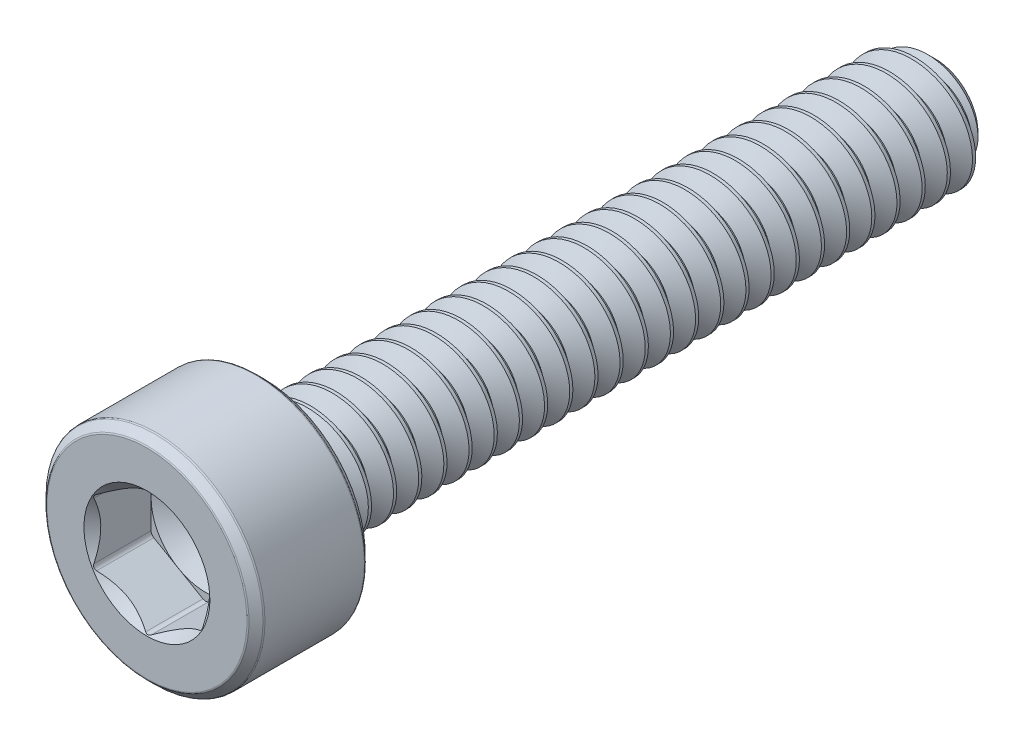
SolidWorks part; units mm, degrees
ref_plane "Front Plane" through (0, 0, 0) normal (0, 0, 1) x (1, 0, 0)
ref_plane "Top Plane" through (0, 0, 0) normal (0, 1, 0) x (1, 0, 0)
ref_plane "Right Plane" through (0, 0, 0) normal (1, 0, 0) x (0, 0, -1)
sketch "Sketch1" plane through (0, 0, 0) normal (1, 0, 0) x (0, 0, -1)
  line L0 (-4.7, 0) -> (4.7, 0) construction
  line L1 (-4.7, 0) -> (-4.7, 1.3)
  line L2 (-4.7, 1.3) -> (-3.3, 1.3)
  line L3 (-3.3, 1.3) -> (-3.3, 0.7)
  line L4 (-3.3, 0.7) -> (4.5051, 0.7)
  line L5 (4.6812, 0.7325) -> (4.8312, 0.4727) construction
  line L6 (4.8312, 0.4727) -> (4.9812, 0.7325) construction
  line L7 (4.9812, 0.7325) -> (4.6812, 0.7325) construction
  line L8 (4.5051, 0.7) -> (4.7, 0.5051)
  line L9 (4.7, 0.5051) -> (4.7, 0)
  line L10 (4.7, 0.7) -> (4.9625, 0.7) construction
  line L11 (4.8312, 0.7325) -> (4.8312, 0.7) construction
  line L12 (4.8312, 0.7) -> (4.8312, 0.5051) construction
  line L13 (4.8312, 0.5051) -> (4.8312, 0.4727) construction
  line L14 (4.8125, 0.5051) -> (4.85, 0.5051)
  line L15 (4.6906, 0.7162) -> (4.9719, 0.7162)
  line L16 (4.85, 0.5051) -> (4.9719, 0.7162)
  line L17 (4.8125, 0.5051) -> (4.6906, 0.7162)
  line L18 (-4.7, 0.65) -> (-4, 0.65)
  line L19 (-4, 0.65) -> (-4, 0)
  line L20 (3.65, 0.7) -> (3.65, -0.7) construction
  point P20 (4.8312, 0.7162)
  point P22 (3.65, -0.7)
  point P28 (3.65, 0)
  point P29 (4.5051, -0.7)
  dimension "Head Diameter" = 2.6
  dimension "Length" = 8
  dimension "Head Height" = 1.4
  dimension "Thread Size" = 1.4
  dimension "D1" = 45
  dimension "Thread Pitch" = 0.3
  dimension "D3" = 0.0375
  dimension "Drive Size" = 1.3
  dimension "D4" = 1.05
  dimension "D5" = 0.7
sketch "Sketch3" plane through (0, 0, 0) normal (1, 0, 0) x (0, 0, -1)
  line L0 (-4.7, 1.1924) -> (-4.7, 0.65)
  line L1 (-4.7, 0.65) -> (-4, 0.65)
  line L2 (-4, 0.65) -> (-4, 0)
  line L3 (-4, 0) -> (4.7, 0)
  line L4 (4.7, 0) -> (4.7, 0.5051)
  line L5 (4.7, 0.5051) -> (4.5051, 0.7)
  line L6 (4.5051, 0.7) -> (-3.3, 0.7)
  line L7 (-3.3, 0.7) -> (-3.3, 1.1924)
  line L8 (-3.4076, 1.3) -> (-4.5924, 1.3)
  line L9 (-4.6929, 1.2096) -> (-4.6096, 1.2929)
  line L11 (-4.7, 1.3) -> (-3.3, 1.3) construction
  line L12 (-3.3904, 1.2929) -> (-3.3071, 1.2096)
  arc A5 (-3.3071, 1.2096) -> (-3.3, 1.1924) centre (-3.3244, 1.1924) cw
  arc A6 (-3.4076, 1.3) -> (-3.3904, 1.2929) centre (-3.4076, 1.2756) cw
  arc A7 (-4.5924, 1.3) -> (-4.6096, 1.2929) centre (-4.5924, 1.2756) ccw
  arc A8 (-4.7, 1.1924) -> (-4.6929, 1.2096) centre (-4.6756, 1.1924) cw
  point P17 (-4, 1.3)
  point P29 (-4.7, 1.2025)
  dimension "D3" = 0.0244
  dimension "D1" = 45
  dimension "D2" = 0.0975
revolve "Revolve1" add sketch "Sketch3" angle 360 about L0
sketch "Sketch4" plane through (0, 0, 4.7) normal (0, 0, 1) x (1, 0, 0)
  line L1 (0, 0.7506) -> (-0.65, 0.3753)
  line L2 (-0.65, 0.3753) -> (-0.65, -0.3753)
  line L3 (-0.65, -0.3753) -> (0, -0.7506)
  line L4 (0, -0.7506) -> (0.65, -0.3753)
  line L5 (0.65, -0.3753) -> (0.65, 0.3753)
  line L6 (0.65, 0.3753) -> (0, 0.7506)
  circle A0 centre (0, 0) radius 0.65 construction
extrude "Cut-Extrude1" cut sketch "Sketch4" against normal up to vertex (0.7 mm away) up to point (0, 0.65, 4)
sketch "Sketch5" plane through (0, 0, 4.7) normal (0, 0, 1) x (1, 0, 0)
  circle A0 centre (0, 0) radius 0.7506
extrude "Cut-Extrude2" cut sketch "Sketch5" against normal up to next (0.7 mm away) draft 45
sketch "Sketch10" plane through (0, 0, 4) normal (0, 0, 1) x (1, 0, 0)
  line L0 (0.65, 0.3753) -> (0.65, -0.3753) construction
  circle A0 centre (0, 0) radius 0.65
extrude "Cut-Extrude3" cut sketch "Sketch10" against normal through all draft 60
fillet "Fillet1" radius 0.065 6 edges at (-0.65, 0.3753, 4.35) (0, 0.7506, 4.35) (0.65, 0.3753, 4.35) (0.65, -0.3753, 4.35) (0, -0.7506, 4.35) (-0.65, -0.3753, 4.35)
sketch "Sketch6" plane through (0, 0, -4.7) normal (0, 0, -1) x (-1, 0, 0)
  circle A0 centre (0, 0) radius 0.7 construction
  circle A1 centre (0, 0) radius 0.7
curve "Helix/Spiral1" pitch 0.3 height 8.3 radius 0.7 centre (0, 0, -4.7) axis (0, 0, 1) start towards (0, 1, 0)
sketch "Sketch7" plane through (0, 0, 0) normal (1, 0, 0) x (0, 0, -1)
  line L0 (4.8125, 0.5051) -> (4.85, 0.5051) construction
  line L1 (4.8125, 0.5051) -> (4.6906, 0.7162) construction
  line L2 (4.6906, 0.7162) -> (4.9719, 0.7162) construction
  line L3 (4.85, 0.5051) -> (4.9719, 0.7162) construction
  line L4 (4.8125, 0.5051) -> (4.85, 0.5051)
  line L5 (4.8125, 0.5051) -> (4.6906, 0.7162)
  line L6 (4.6906, 0.7162) -> (4.9719, 0.7162)
  line L7 (4.85, 0.5051) -> (4.9719, 0.7162)
sweep "Cut-Sweep1" cut profiles "Sketch7" path "Helix/Spiral1" align with end faces yes
sketch "Sketch11" plane through (0, 0, 0) normal (1, 0, 0) x (0, 0, -1)
  line L0 (-3.3, 0.775) -> (-3.225, 0.7) construction
  line L1 (-3.3, 1.3) -> (-3.3, 0.7) construction
  line L2 (-3.3, 0.7) -> (4.5051, 0.7) construction
  line L3 (-3.225, 0.7) -> (-3.15, 0.7)
  line L4 (-3.15, 0.7) -> (-2.45, 0)
  line L5 (-4.7, 0) -> (4.7, 0) construction
  line L6 (-2.45, 0) -> (-3.3, 0)
  line L7 (-3.3, 0) -> (-3.3, 0.775) construction
  line L8 (-3.3, 0.775) -> (-3.6247, 0.775)
  line L9 (-3.6247, 0.775) -> (-3.6247, 0)
  line L10 (-3.6247, 0) -> (-3.3, 0)
  arc A0 (-3.225, 0.7) -> (-3.3, 0.775) centre (-3.225, 0.775) cw
  dimension "D1" = 45
  dimension "D2" = 0.075
  dimension "D3" = 45
  dimension "D4" = 0.15
revolve "Revolve2" add sketch "Sketch11" angle 360 about L6
equation "\"D3@Sketch1\" = \"Thread Pitch@Sketch1\" / 8"
equation "\"D4@Sketch1\" = \"Thread Pitch@Sketch1\" * 3.5"
equation "\"D3@Helix/Spiral1\" = \"Length@Sketch1\" + \"Thread Pitch@Sketch1\""
equation "\"D4@Helix/Spiral1\" = \"Thread Pitch@Sketch1\""
equation "\"D5@Sketch1\"=\"Head Height@Sketch1\"*0.5"
equation "\"D2@Sketch3\"=\"Head Diameter@Sketch1\" *0.0375"
equation "\"D2@Sketch11\"=\"Thread Pitch@Sketch1\" / 4"
equation "\"D4@Sketch11\"=\"Thread Pitch@Sketch1\"/2"
equation "\"D1@Fillet1\"=\"Drive Size@Sketch1\"*0.05"
equation "\"D1@Fillet1\" = \"Drive Size@Sketch1\" * 0.05"
equation "\"D3@Sketch3\"=\"D2@Sketch3\"*0.25"
